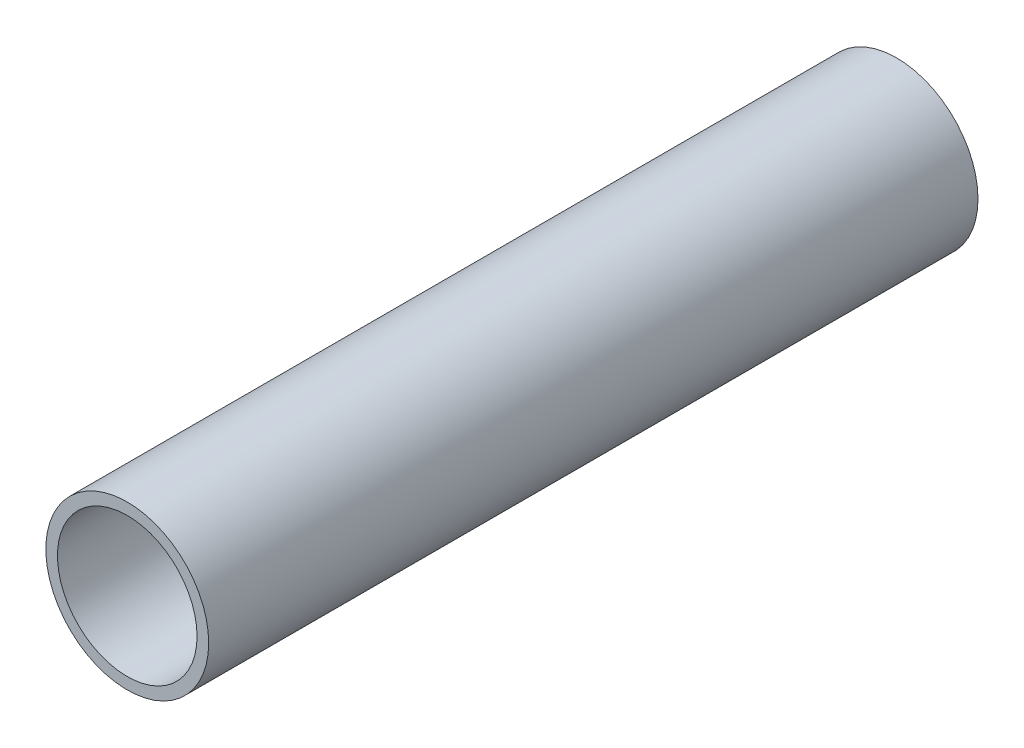
SolidWorks part; units mm, degrees
ref_plane "Front Plane" through (0, 0, 0) normal (0, 0, 1) x (1, 0, 0)
ref_plane "Top Plane" through (0, 0, 0) normal (0, 1, 0) x (1, 0, 0)
ref_plane "Right Plane" through (0, 0, 0) normal (1, 0, 0) x (0, 0, -1)
sketch "Sketch1" plane through (0, 0, 0) normal (0, 0, 1) x (1, 0, 0)
  circle A0 centre (0, 0) radius 38.1
  circle A1 centre (0, 0) radius 44.45
  dimension "D1" = 88.9
  dimension "D2" = 6.35
extrude "Boss-Extrude1" add sketch "Sketch1" along normal blind 420
